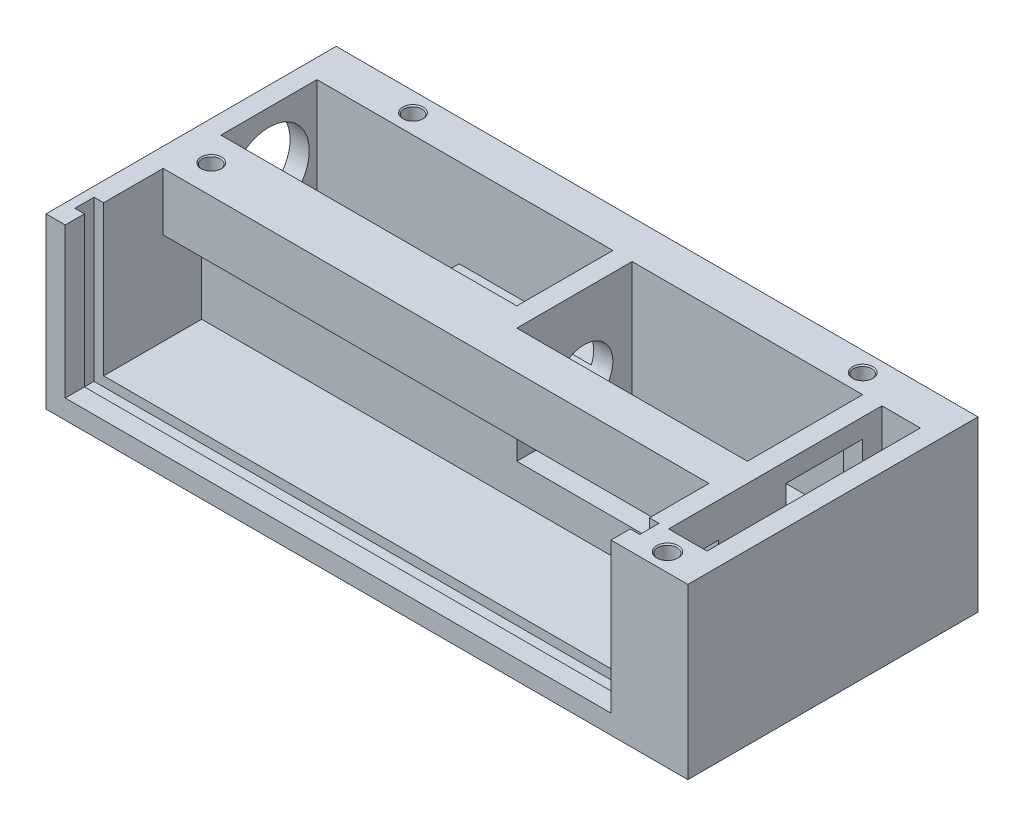
SolidWorks part; units mm, degrees
ref_plane "Front Plane" through (0, 0, 0) normal (0, 0, 1) x (1, 0, 0)
ref_plane "Top Plane" through (0, 0, 0) normal (0, 1, 0) x (1, 0, 0)
ref_plane "Right Plane" through (0, 0, 0) normal (1, 0, 0) x (0, 0, -1)
sketch "Sketch1" plane through (0, 0, 0) normal (0, 1, 0) x (1, 0, 0)
  line L1 (76, -32.75) -> (-76, -32.75)
  line L2 (76, -32.75) -> (76, 32.75)
  line L3 (76, 32.75) -> (-76, 32.75)
  line L4 (-76, -32.75) -> (-76, 32.75)
  line L5 (76, -32.75) -> (-76, 32.75) construction
  line L6 (76, 32.75) -> (-76, -32.75) construction
  point P0 (0, 0)
  dimension "D1" = 152
  dimension "D2" = 65.5
extrude "Boss-Extrude1" add sketch "Sketch1" along normal blind 44
sketch "Sketch2" plane through (0, 44, 0) normal (0, 1, 0) x (1, 0, 0)
  line L6 (-76, -32.75) -> (76, -32.75) construction
  line L7 (-76, 32.75) -> (-76, -32.75) construction
  line L8 (-71, -32.75) -> (71, -32.75)
  line L9 (-71, -32.75) -> (-71, -7.25)
  line L10 (-71, -7.25) -> (71, -7.25)
  line L11 (71, -32.75) -> (71, -7.25)
  line M6 (-76, -32.75) -> (76, -32.75)
  dimension "D5" = 25.5
  dimension "D6" = 5
  dimension "D7" = 142
extrude "Cut-Extrude1" cut sketch "Sketch2" against normal blind 39 contours L11 L10 L9 M6 region at (0, 44, 20)
sketch "Sketch4" plane through (0, 44, 0) normal (0, 1, 0) x (1, 0, 0)
  line L0 (76, -32.75) -> (76, 32.75) construction
  line L1 (11, 22.75) -> (71, 22.75)
  line L2 (11, 22.75) -> (11, -7.25)
  line L3 (11, -7.25) -> (71, -7.25)
  line L4 (71, 22.75) -> (71, -7.25)
  line L7 (-71, -7.25) -> (71, -7.25) construction
  dimension "D1" = 30
  dimension "D2" = 60
  dimension "D3" = 5
extrude "Cut-Extrude2" cut sketch "Sketch4" against normal blind 30
sketch "Sketch5" plane through (-71, 0, 0) normal (1, 0, 0) x (0, 0, -1)
  line L1 (-7.25, 44) -> (-17.25, 44)
  line L2 (-7.25, 44) -> (-7.25, 29)
  line L3 (-7.25, 29) -> (-17.25, 29)
  line L4 (-17.25, 44) -> (-17.25, 29)
  dimension "D1" = 10
  dimension "D2" = 15
extrude "Boss-Extrude3" add sketch "Sketch5" along normal up to surface (142 mm away) up to face at (71, 21, 5.75)
sketch "Sketch9" plane through (0, 0, 32.75) normal (0, 0, 1) x (1, 0, 0)
  line L0 (-76, 0) -> (76, 0) construction
  line L1 (-76, 44) -> (76, 44)
  line L2 (-76, 44) -> (-76, 0)
  line L3 (-76, 0) -> (76, 0)
  line L4 (76, 44) -> (76, 0)
  line L5 (71, 5) -> (71, 44) construction
  dimension "D1" = 5
extrude "Boss-Extrude4" add sketch "Sketch9" along normal blind 10
sketch "Sketch10" plane through (0, 44, 0) normal (0, 1, 0) x (1, 0, 0)
  line L0 (-76, 32.75) -> (-76, -42.75) construction
  line L1 (-73.5, -37.75) -> (73.5, -37.75)
  line L2 (-73.5, -37.75) -> (-73.5, -32.75)
  line L3 (-73.5, -32.75) -> (73.5, -32.75)
  line L4 (73.5, -37.75) -> (73.5, -32.75)
  line L5 (76, -42.75) -> (76, 32.75) construction
  line L6 (71, -32.75) -> (-71, -32.75) construction
  line M5 (71, -32.75) -> (-71, -32.75)
  dimension "D1" = 5
  dimension "D2" = 2.5
  dimension "D3" = 2.5
extrude "Cut-Extrude5" cut sketch "Sketch10" against normal offset from surface (41.5 mm away) 2.5 contours L1 L4 L3 L2 M5 region at (0, 44, 35.25) up to face at (0, 0, 5)
sketch "Sketch11" plane through (0, 0, 42.75) normal (0, 0, 1) x (1, 0, 0)
  line L0 (71, 5) -> (71, 44) construction
  line L1 (71, 5) -> (71, 44)
  line L2 (-71, 5) -> (-71, 44) construction
  line L4 (-76, 44) -> (-76, 0)
  line L5 (-76, 0) -> (76, 0)
  line L6 (76, 0) -> (76, 44)
  line L7 (76, 44) -> (-76, 44)
  line L8 (-76, 44) -> (-76, 0)
  line L9 (-76, 0) -> (76, 0)
  line L10 (76, 0) -> (76, 44)
  line L11 (76, 44) -> (-76, 44)
  line L12 (-71, 5) -> (-71, 44)
  line L13 (-71, 5) -> (71, 5)
  line L14 (71, 5) -> (71, 44)
  line L15 (-71, 44) -> (71, 44)
  line M8 (76, 44) -> (-76, 44)
  dimension "D1" = 0
extrude "Cut-Extrude6" cut sketch "Sketch11" against normal up to surface (5 mm away) contours L12 L13 L1 M8 region at (0, 24.5, 42.75) up to face at (0, 23.25, 37.75)
sketch "Sketch16" plane through (0, 44, 0) normal (0, 1, 0) x (1, 0, 0)
  line L0 (76, 32.75) -> (-76, 32.75) construction
  line L1 (-71, 22.75) -> (6, 22.75)
  line L2 (-71, 22.75) -> (-71, -2.25)
  line L3 (-71, -2.25) -> (6, -2.25)
  line L4 (6, 22.75) -> (6, -2.25)
  line L5 (-76, 32.75) -> (-76, -42.75) construction
  line L6 (11, 22.75) -> (11, -7.25) construction
  line L7 (71, -7.25) -> (11, -7.25) construction
  dimension "D1" = 10
  dimension "D2" = 5
  dimension "D3" = 5
  dimension "D4" = 5
extrude "Cut-Extrude8" cut sketch "Sketch16" against normal offset from surface (39 mm away) 5 up to face at (0, 0, 5)
sketch "Sketch17" plane through (-71, 0, 0) normal (1, 0, 0) x (0, 0, -1)
  line L0 (7.5, 10) -> (13, 10) construction
  line L1 (7.5, 12) -> (13, 12)
  line L2 (7.5, 8) -> (13, 8)
  line L7 (-2.25, 5) -> (22.75, 5)
  line L8 (22.75, 5) -> (22.75, 44)
  line L9 (22.75, 44) -> (-2.25, 44)
  line L10 (-2.25, 44) -> (-2.25, 5)
  line L11 (-2.25, 5) -> (22.75, 5)
  line L12 (22.75, 5) -> (22.75, 44)
  line L13 (22.75, 44) -> (-2.25, 44)
  line L14 (-2.25, 44) -> (-2.25, 5)
  circle A0 centre (10.25, 29) radius 10.5
  arc A1 (7.5, 12) -> (7.5, 8) centre (7.5, 10) ccw
  arc A2 (13, 8) -> (13, 12) centre (13, 10) ccw
  point P4 (10.25, 10)
  point P9 (5.5, 10)
  point P10 (15, 10)
  point P14 (10.25, 5)
  dimension "D1" = 21
  dimension "D2" = 9.5
  dimension "D3" = 4
  dimension "D5" = 3
  dimension "D6" = 15
  dimension "D4" = 0
extrude "Cut-Extrude9" cut sketch "Sketch17" against normal up to surface (5 mm away) contours A0 | L2 A2 L1 A1 region at (-71, 10, -10.25) region at (-71, 29, -10.25) up to face at (-76, 22, 5)
sketch "Sketch18" plane through (11, 0, 0) normal (1, 0, 0) x (0, 0, -1)
  line L16 (22.75, 44) -> (-7.25, 44)
  line L17 (-7.25, 44) -> (-7.25, 29)
  line L18 (-7.25, 29) -> (-7.25, 14)
  line L19 (-7.25, 14) -> (22.75, 14)
  line L20 (22.75, 14) -> (22.75, 44)
  line L21 (22.75, 44) -> (-7.25, 44)
  line L22 (-7.25, 44) -> (-7.25, 29)
  line L23 (-7.25, 29) -> (-7.25, 14)
  line L24 (-7.25, 14) -> (22.75, 14)
  line L25 (22.75, 14) -> (22.75, 44)
  circle A0 centre (10.25, 24) radius 7.5
  dimension "D1" = 15
  dimension "D3" = 10
  dimension "D4" = 12.5
  dimension "D2" = 0
extrude "Cut-Extrude10" cut sketch "Sketch18" against normal up to surface (5 mm away) contours A0 region at (11, 24, -10.25) up to face at (6, 24.5, -10.25)
sketch "Sketch20" plane through (76, 0, 0) normal (1, 0, 0) x (0, 0, -1)
  line L1 (-42.75, 44) -> (32.75, 44)
  line L2 (-42.75, 44) -> (-42.75, 0)
  line L3 (-42.75, 0) -> (32.75, 0)
  line L4 (32.75, 44) -> (32.75, 0)
extrude "Boss-Extrude6" add sketch "Sketch20" along normal blind 15
sketch "Sketch21" plane through (0, 44, 0) normal (0, 1, 0) x (1, 0, 0)
  line L0 (91, 32.75) -> (91, -42.75) construction
  line L1 (76, 22.75) -> (86, 22.75)
  line L2 (76, 22.75) -> (76, -32.75)
  line L3 (76, -32.75) -> (86, -32.75)
  line L4 (86, 22.75) -> (86, -32.75)
  line L5 (71, 22.75) -> (11, 22.75) construction
  line L6 (71, -32.75) -> (73.5, -32.75) construction
  dimension "D1" = 5
  dimension "D2" = 10
extrude "Cut-Extrude12" cut sketch "Sketch21" against normal offset from surface (39 mm away) 5 up to face at (7.5, 0, 5)
sketch "Sketch22" plane through (76, 0, 0) normal (1, 0, 0) x (0, 0, -1)
  line L2 (22.75, 5) -> (22.75, 44) construction
  line L3 (-2.25, 39) -> (17.75, 39)
  line L4 (-2.25, 39) -> (-2.25, 19)
  line L5 (-2.25, 19) -> (17.75, 19)
  line L6 (17.75, 39) -> (17.75, 19)
  line L8 (-7.25, 14) -> (22.75, 14) construction
  line L9 (-32.75, 5) -> (22.75, 5) construction
  line L10 (-27.25, 35) -> (-19.75, 35)
  line L11 (-27.25, 35) -> (-27.25, 10)
  line L12 (-27.25, 10) -> (-19.75, 10)
  line L13 (-19.75, 35) -> (-19.75, 10)
  line L14 (-17.25, 44) -> (-17.25, 29) construction
  dimension "D1" = 25
  dimension "D2" = 7.5
  dimension "D3" = 5
  dimension "D4" = 20
  dimension "D5" = 20
  dimension "D6" = 5
  dimension "D7" = 5
  dimension "D8" = 2.5
extrude "Cut-Extrude13" cut sketch "Sketch22" against normal up to surface (5 mm away) contours L6 L3 L4 L5 | L13 L10 L11 L12 region at (76, 29, -7.75) region at (76, 22.5, 23.5) up to face at (71, 27.2, 8.35)
sketch "Sketch23" plane through (-71, 0, 0) normal (1, 0, 0) x (0, 0, -1)
  line L0 (7.5, 12) -> (13, 12) construction
  line L1 (7.5, 12) -> (13, 12)
  line L2 (7.5, 8) -> (13, 8) construction
  line L3 (7.5, 8) -> (13, 8)
  line L4 (-2.25, 5) -> (22.75, 5)
  line L5 (22.75, 5) -> (22.75, 44)
  line L6 (22.75, 44) -> (-2.25, 44)
  line L7 (-2.25, 44) -> (-2.25, 5)
  line L8 (-2.25, 5) -> (22.75, 5)
  line L9 (22.75, 5) -> (22.75, 44)
  line L10 (22.75, 44) -> (-2.25, 44)
  line L11 (-2.25, 44) -> (-2.25, 5)
  line L13 (4.25, 12) -> (16.25, 12)
  line L14 (4.25, 12) -> (4.25, 5)
  line L15 (4.25, 5) -> (16.25, 5)
  line L16 (16.25, 12) -> (16.25, 5)
  line L17 (4.25, 12) -> (16.25, 5) construction
  line L18 (4.25, 5) -> (16.25, 12) construction
  arc A0 (13, 8) -> (13, 12) centre (13, 10) ccw construction
  arc A1 (7.5, 12) -> (7.5, 8) centre (7.5, 10) ccw construction
  arc A2 (13, 8) -> (13, 12) centre (13, 10) ccw
  arc A3 (7.5, 12) -> (7.5, 8) centre (7.5, 10) ccw
  point P10 (10.25, 8.5)
  point P16 (10.25, 8)
  arc M7 (13, 12) -> (13, 8) centre (13, 10) cw
  line M8 (13, 8) -> (7.5, 8)
  arc M9 (7.5, 8) -> (7.5, 12) centre (7.5, 10) cw
  dimension "D2" = 12
  dimension "D1" = 0
extrude "Cut-Extrude14" cut sketch "Sketch23" against normal offset from surface (3.5 mm away) 1.5 contours L16 L13 L14 L8 M7 M8 M9 region at (-71, 7.4511, -10.25) up to face at (-76, 29, -20.75)
sketch "Sketch24" plane through (0, 5, 0) normal (0, 1, 0) x (1, 0, 0)
  line L1 (-71, 16.25) -> (-66, 16.25)
  line L2 (-71, 16.25) -> (-71, 22.75)
  line L3 (-71, 22.75) -> (-66, 22.75)
  line L4 (-66, 16.25) -> (-66, 22.75)
  line L5 (-71, 4.25) -> (-66, 4.25)
  line L6 (-71, 4.25) -> (-71, -2.25)
  line L7 (-71, -2.25) -> (-66, -2.25)
  line L8 (-71, 4.25) -> (-71, -2.25)
  line L9 (-71, -2.25) -> (6, -2.25)
  line L10 (6, -2.25) -> (6, 22.75)
  line L11 (6, 22.75) -> (-71, 22.75)
  line L12 (-71, 22.75) -> (-71, 16.25)
  line L13 (-71, 16.25) -> (-74.5, 16.25)
  line L14 (-74.5, 16.25) -> (-74.5, 4.25)
  line L15 (-74.5, 4.25) -> (-71, 4.25)
  line L16 (-71, 4.25) -> (-71, -2.25)
  line L17 (-71, -2.25) -> (6, -2.25)
  line L18 (6, -2.25) -> (6, 22.75)
  line L19 (6, 22.75) -> (-71, 22.75)
  line L20 (-71, 22.75) -> (-71, 16.25)
  line L21 (-71, 16.25) -> (-74.5, 16.25)
  line L22 (-74.5, 16.25) -> (-74.5, 4.25)
  line L23 (-74.5, 4.25) -> (-71, 4.25)
  line L24 (-66, 4.25) -> (-66, -2.25)
  line L25 (-48, 16.25) -> (-45, 16.25)
  line L26 (-48, 16.25) -> (-48, 4.25)
  line L27 (-48, 4.25) -> (-45, 4.25)
  line L28 (-45, 16.25) -> (-45, 4.25)
  line L29 (-48, 16.25) -> (-45, 4.25) construction
  line L30 (-48, 4.25) -> (-45, 16.25) construction
  line L31 (-45, 4.25) -> (-50, 4.25)
  line L32 (-45, 4.25) -> (-45, -2.25)
  line L33 (-45, -2.25) -> (-50, -2.25)
  line L34 (-50, 4.25) -> (-50, -2.25)
  line L35 (-45, 22.75) -> (-50, 22.75)
  line L36 (-45, 22.75) -> (-45, 16.25)
  line L37 (-45, 16.25) -> (-50, 16.25)
  line L38 (-50, 22.75) -> (-50, 16.25)
  point P14 (-46.5, 10.25)
  point P20 (-74.5, 10.25)
  line M16 (-71, 4.25) -> (-71, -2.25)
  line M17 (-71, -2.25) -> (6, -2.25)
  line M19 (6, 22.75) -> (-71, 22.75)
  line M20 (-71, 22.75) -> (-71, 16.25)
  dimension "D2" = 5
  dimension "D3" = 5
  dimension "D4" = 12
  dimension "D5" = 3
  dimension "D6" = 26.5
  dimension "D7" = 5
  dimension "D8" = 5
  dimension "D1" = 0
extrude "Boss-Extrude7" add sketch "Sketch24" along normal blind 5 contours L24 L5 M16 M17 | L1 L4 M19 M20 | L31 L34 L17 L32 L27 | L19 L38 L37 L25 L36 region at (-68.5, 5, -19.5) region at (-47.5, 5, -19.5) region at (-68.5, 5, -1) region at (-47.5, 5, -1)
extrude "Boss-Extrude8" add sketch "Sketch24<3>" along normal blind 2.5 contours L28 L25 L26 L27 region at (-46.5, 5, -10.25)
sketch "Sketch24<3>" plane through (0, 5, 0) normal (0, 1, 0) x (1, 0, 0) same geometry as "Sketch24"
sketch "Sketch13" plane through (0, 0, -32.75) normal (0, 0, -1) x (-1, 0, 0)
  line L0 (-81, 34) -> (-81, 24) construction
  line L1 (-76, 34) -> (-76, 24)
  line L2 (-86, 34) -> (-86, 24)
  line L3 (-91, 44) -> (76, 44) construction
  line L5 (66, 34) -> (66, 24) construction
  line L6 (71, 34) -> (71, 24)
  line L7 (61, 34) -> (61, 24)
  line L8 (76, 44) -> (76, 0) construction
  line L9 (-91, 0) -> (-91, 44) construction
  arc A0 (-76, 34) -> (-86, 34) centre (-81, 34) ccw
  arc A1 (-86, 24) -> (-76, 24) centre (-81, 24) ccw
  arc A2 (71, 34) -> (61, 34) centre (66, 34) ccw
  arc A3 (61, 24) -> (71, 24) centre (66, 24) ccw
  point P2 (-81, 29)
  point P11 (66, 29)
  point P12 (-81, 39)
  point P13 (-81, 19)
  point P22 (66, 39)
  point P23 (66, 19)
  dimension "D1" = 5
  dimension "D5" = 5
  dimension "D2" = 10
  dimension "D3" = 10
  dimension "D4" = 20
  dimension "D6" = 10
  dimension "D7" = 10
  dimension "D8" = 20
extrude "Cut-Extrude7" cut sketch "Sketch13" against normal blind 6 contours L2 A1 L1 A0 | L7 A3 L6 A2 region at (81, 29, -32.75) region at (-66, 29, -32.75)
sketch "Sketch15" plane through (0, 0, -32.75) normal (0, 0, -1) x (-1, 0, 0)
  line L0 (61, 34) -> (61, 24) construction
  line L1 (71, 24) -> (71, 34) construction
  line L2 (-86, 34) -> (-86, 24) construction
  line L3 (-76, 24) -> (-76, 34) construction
  line L4 (-91, 0) -> (76, 0)
  line L5 (76, 0) -> (76, 44)
  line L6 (76, 44) -> (-91, 44)
  line L7 (-91, 44) -> (-91, 0)
  line L8 (-91, 0) -> (76, 0)
  line L9 (76, 0) -> (76, 44)
  line L10 (76, 44) -> (-91, 44)
  line L12 (61, 34) -> (61, 24)
  line L13 (71, 24) -> (71, 34)
  line L14 (-86, 34) -> (-86, 24)
  line L15 (-76, 24) -> (-76, 34)
  line L16 (-83, 34) -> (-79, 34)
  line L17 (-83, 34) -> (-83, 28.5826)
  line L18 (-79, 34) -> (-79, 28.5826)
  line L19 (64, 34) -> (68, 34)
  line L20 (64, 34) -> (64, 28.5826)
  line L21 (68, 34) -> (68, 28.5826)
  line L26 (-91, 44) -> (-91, 0)
  arc A0 (61, 24) -> (71, 24) centre (66, 24) ccw construction
  arc A1 (71, 34) -> (61, 34) centre (66, 34) ccw construction
  arc A2 (-86, 24) -> (-76, 24) centre (-81, 24) ccw construction
  arc A3 (-76, 34) -> (-86, 34) centre (-81, 34) ccw construction
  arc A4 (61, 24) -> (71, 24) centre (66, 24) ccw
  arc A5 (71, 34) -> (61, 34) centre (66, 34) ccw
  arc A6 (-86, 24) -> (-76, 24) centre (-81, 24) ccw
  arc A7 (-76, 34) -> (-86, 34) centre (-81, 34) ccw
  circle A8 centre (-81, 24) radius 5
  circle A9 centre (66, 24) radius 5
  point P20 (-81, 34)
  point P26 (66, 34)
  line M7 (-86, 24) -> (-86, 34)
  arc M8 (-86, 34) -> (-76, 34) centre (-81, 34) cw
  line M9 (-76, 34) -> (-76, 24)
  line M11 (61, 24) -> (61, 34)
  arc M12 (61, 34) -> (71, 34) centre (66, 34) cw
  line M13 (71, 34) -> (71, 24)
  dimension "D2" = 4
  dimension "D3" = 4
  dimension "D1" = 0
extrude "Boss-Extrude5" add sketch "Sketch15" against normal blind 3 contours A8 L17 L16 L18 M9 M8 M7 | A9 L20 L19 L21 M13 M12 M11 region at (-66, 38.8197, -32.75) region at (81, 38.8197, -32.75)
sketch "Sketch19" plane through (0, 44, 0) normal (0, 1, 0) x (1, 0, 0)
  line L0 (91, 32.75) -> (91, -42.75) construction
  line L1 (91, 32.75) -> (-76, 32.75) construction
  line L2 (91, -42.75) -> (71, -42.75) construction
  line L4 (-76, 32.75) -> (-76, -42.75) construction
  line L5 (-71, -2.25) -> (6, -2.25) construction
  circle A0 centre (-66, -9.75) radius 2.35
  circle A1 centre (-51, 27.75) radius 2.35
  circle A2 centre (66, 27.75) radius 2.35
  circle A3 centre (81, -38.05) radius 2.5
  dimension "D1" = 4.7
  dimension "D2" = 4.7
  dimension "D3" = 4.7
  dimension "D9" = 5
  dimension "D4" = 5
  dimension "D5" = 25
  dimension "D6" = 25
  dimension "D7" = 10
  dimension "D8" = 7.5
  dimension "D10" = 10
  dimension "D11" = 4.7
extrude "Cut-Extrude11" cut sketch "Sketch19" against normal blind 6
sketch "Sketch25" plane through (6, 0, 0) normal (-1, 0, 0) x (0, 0, 1)
  line L0 (-22.75, 5) -> (-22.75, 44) construction
  line L1 (-22.75, 18.5) -> (-15.25, 18.5)
  line L2 (-22.75, 18.5) -> (-22.75, 21)
  line L3 (-22.75, 21) -> (-15.25, 21)
  line L4 (-15.25, 18.5) -> (-15.25, 21)
  line L5 (2.25, 44) -> (-22.75, 44) construction
  line L6 (2.25, 5) -> (2.25, 44) construction
  line L7 (2.25, 21) -> (-5.25, 21)
  line L8 (2.25, 21) -> (2.25, 18.5)
  line L9 (2.25, 18.5) -> (-5.25, 18.5)
  line L10 (-5.25, 21) -> (-5.25, 18.5)
  line L11 (-16.25, 21) -> (-16.25, 18.5)
  line L12 (-4.25, 21) -> (-4.25, 18.5)
  circle M7 centre (-10.25, 24) radius 7.5
  line M9 (2.25, 5) -> (2.25, 44)
  line M11 (-22.75, 44) -> (-22.75, 5)
  dimension "D1" = 7.5
  dimension "D2" = 23
  dimension "D3" = 2.5
  dimension "D4" = 23
  dimension "D5" = 2.5
  dimension "D6" = 7.5
  dimension "D7" = 1
  dimension "D8" = 1
extrude "Boss-Extrude9" add sketch "Sketch25" along normal blind 40 contours L3 L1 M11 M7 | L9 L7 M9 M7 region at (6, 19.7165, -19.6353) region at (6, 19.7165, -0.8647)
chamfer "Chamfer1" distance 0.3 angle 45 4 edges at (81, 44, 40.55) (66, 44, -25.4) (-51, 44, -25.4) (-66, 44, 12.1)
